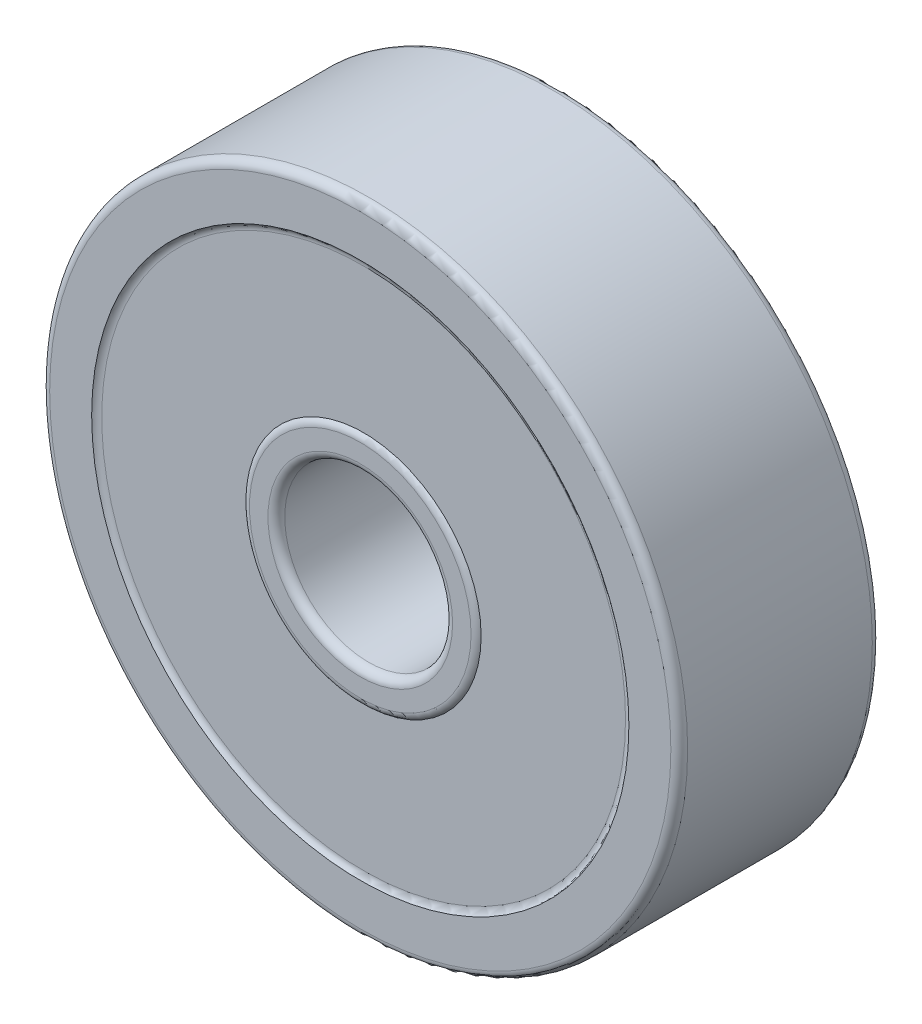
SolidWorks part; units mm, degrees
material "1.4000 (X6Cr13)"
ref_plane "Plan de face" through (0, 0, 0) normal (0, 0, 1) x (1, 0, 0)
ref_plane "Plan de dessus" through (0, 0, 0) normal (0, 1, 0) x (1, 0, 0)
ref_plane "Plan de droite" through (0, 0, 0) normal (1, 0, 0) x (0, 0, -1)
sketch "Esquisse1" plane through (0, 0, 0) normal (0, 0, 1) x (1, 0, 0)
  circle A0 centre (0, 0) radius 2.5
  circle A1 centre (0, 0) radius 9.5
extrude "Boss.-Extru.1" add sketch "Esquisse1" along normal blind 3 and the other way blind 3
sketch "Esquisse2" plane through (0, 0, 0) normal (0, 0, 1) x (1, 0, 0)
  circle A0 centre (0, 0) radius 3.5
  circle A1 centre (0, 0) radius 8
extrude "Enlèv. mat.-Extru.1" cut sketch "Esquisse2" against normal blind 6 and the other way blind 6
sketch "Esquisse4" plane through (0, 0, 0) normal (0, 0, 1) x (1, 0, 0)
  circle A0 centre (0, 0) radius 3.5
  circle A1 centre (0, 0) radius 8
extrude "Boss.-Extru.2" add sketch "Esquisse4" along normal blind 2.9 and the other way blind 2.9
fillet "Congé1" radius 0.25 8 edges at (3.5, 0, 3) (9.5, 0, -3) (8, 0, -3) (3.5, 0, -3) (2.5, 0, -3) (8, 0, 2.9) (9.5, 0, 3) (2.5, 0, 3)
